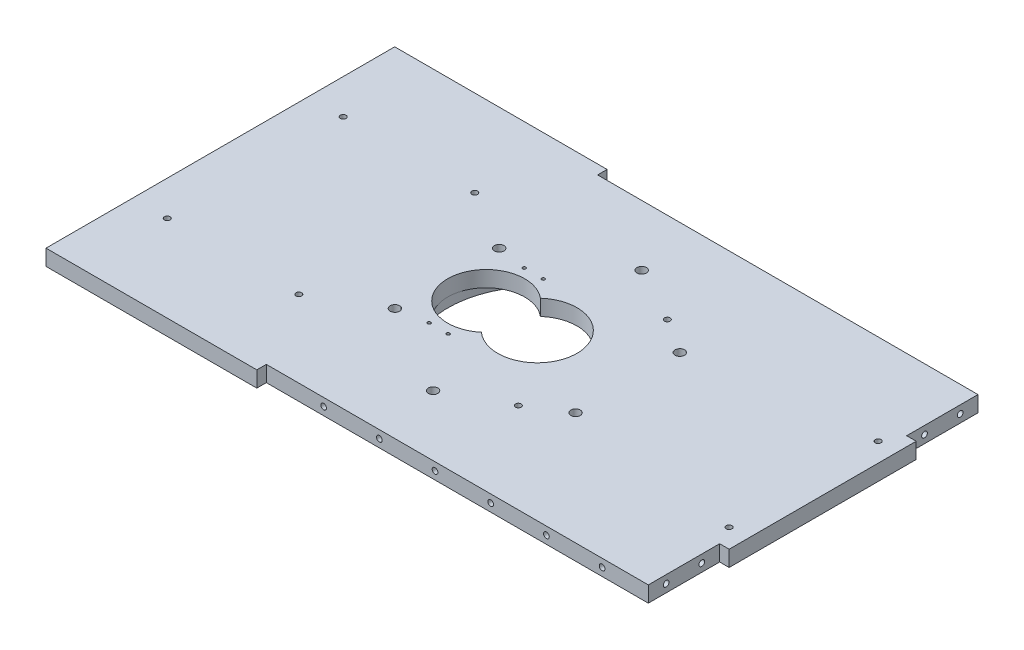
SolidWorks part; units mm, degrees
ref_plane "前视基准面" through (0, 0, 0) normal (0, 0, 1) x (1, 0, 0)
ref_plane "上视基准面" through (0, 0, 0) normal (0, 1, 0) x (1, 0, 0)
ref_plane "右视基准面" through (0, 0, 0) normal (1, 0, 0) x (0, 0, -1)
other "Configuration Table"
sketch "草图1" plane through (0, 0, 0) normal (0, 1, 0) x (1, 0, 0)
  line L0 (-100, 0) -> (90, 0)
  line L1 (-100, 55) -> (90, 55)
  line L2 (-100, 55) -> (-100, -55)
  line L3 (-100, -55) -> (90, -55)
  line L4 (90, 55) -> (90, -55)
  circle A8 centre (0, 0) radius 32.9
  circle A9 centre (0, 0) radius 34.5
  circle A10 centre (0, 0) radius 31.3
  circle A11 centre (0, 0) radius 37.5
  circle A12 centre (0, 0) radius 28.3
  circle A13 centre (-16.15, 0) radius 12.15
  circle A14 centre (0, 32.9) radius 1.5
  circle A15 centre (0, 32.9) radius 0.9
  circle A16 centre (0, 0) radius 12.5
  dimension "D3" = 110
  dimension "D4" = 90
  dimension "D1" = 65.8
  dimension "D2" = 100
  dimension "D5" = 1.6
  dimension "D6" = 1.6
  dimension "D7" = 3
  dimension "D8" = 3
  dimension "D10" = 1.8
  dimension "D11" = 3
  dimension "D12" = 25
  dimension "D9" = 16.15
extrude "凸台-拉伸1" add sketch "草图1" along normal blind 5 contours L3 L4 L1 L2
extrude "凸台-拉伸2" add sketch "草图1<10>" against normal blind 3 contours L0 A11 A9 | L0 A11 A9 | A12 L0 A10 | A12 L0 A10 region at (0, 0, -28.9999) region at (29.8, 0, 0.6999) region at (0, 0, -35.3385) region at (36, 0, 0.8385)
sketch "草图1<10>" plane through (0, 0, 0) normal (0, 1, 0) x (1, 0, 0) same geometry as "草图1"
extrude "切除-拉伸1" cut sketch "草图1<11>" against normal through all both and the other way through all contours L0 A13 | L0 A13 region at (-18.596, 0, 5.643) region at (-18.596, 0, -5.643)
sketch "草图1<11>" plane through (0, 0, 0) normal (0, 1, 0) x (1, 0, 0) same geometry as "草图1"
extrude "切除-拉伸3" cut sketch "草图1<12>" along normal through all contours A15
sketch "草图1<12>" plane through (0, 0, 0) normal (0, 1, 0) x (1, 0, 0) same geometry as "草图1"
extrude "切除-拉伸4" cut sketch "草图1<13>" against normal offset from surface (3.5 mm away) 1.5 from surface contours A14 up to face at (0, 0, 37.5) starting at face at (0, 5, -32)
sketch "草图1<13>" plane through (0, 0, 0) normal (0, 1, 0) x (1, 0, 0) same geometry as "草图1"
pattern_circular "阵列(圆周)1" count 6 over 360 about axis through (0, -3, 0) along (0, 1, 0) of "切除-拉伸3", "切除-拉伸4"
sketch "草图2" plane through (0, 5, 0) normal (0, 1, 0) x (1, 0, 0)
  line L0 (-19.15, -15) -> (-13.15, 15) construction
  line L1 (-13.15, -15) -> (-19.15, 15) construction
  circle A0 centre (-19.15, -15) radius 0.5
  circle A1 centre (-13.15, -15) radius 0.5
  circle A2 centre (-19.15, 15) radius 0.5
  circle A3 centre (-13.15, 15) radius 0.5
  circle A4 centre (-16.15, 0) radius 12.15
  circle A5 centre (-16.15, 0) radius 12.15 construction
  dimension "D1" = 1
  dimension "D2" = 15
  dimension "D3" = 3
extrude "切除-拉伸5" cut sketch "草图2" against normal blind 3 contours A0 | A1 | A2 | A3
extrude "切除-拉伸6" cut sketch "草图1<14>" against normal through all both and the other way through all contours A16
sketch "草图1<14>" plane through (0, 0, 0) normal (0, 1, 0) x (1, 0, 0) same geometry as "草图1"
sketch "草图3" plane through (0, 5, 0) normal (0, 1, 0) x (1, 0, 0)
  line L0 (90, 55) -> (90, -55) construction
  line L1 (17.5, -23.5) -> (17.5, -55) construction
  line L2 (-100, -55) -> (90, -55) construction
  line L3 (17.5, 23.5) -> (17.5, 55) construction
  line L4 (-100, 55) -> (90, 55) construction
  circle A0 centre (17.5, 23.5) radius 0.9
  circle A1 centre (17.5, -23.5) radius 0.9
  circle A2 centre (84, 23.5) radius 0.9
  circle A3 centre (84, -23.5) radius 0.9
  dimension "D1" = 1.8
  dimension "D2" = 47
  dimension "D3" = 66.5
  dimension "D4" = 6
extrude "切除-拉伸7" cut sketch "草图3" against normal blind 3
sketch "草图4" plane through (0, 5, 0) normal (0, 1, 0) x (1, 0, 0)
  circle A0 centre (-89, 27.75) radius 0.9
  circle A1 centre (-47.5, 27.75) radius 0.9
  circle A2 centre (-89, -27.75) radius 0.9
  circle A3 centre (-47.5, -27.75) radius 0.9
  dimension "D3" = 1.8
extrude "切除-拉伸8" cut sketch "草图4" against normal through all contours A2 | A3 | A1 | A0
sketch "草图5" plane through (0, 5, 0) normal (0, 1, 0) x (1, 0, 0)
  line L0 (90, 55) -> (90, -55) construction
  line L1 (90, 55) -> (-33, 55)
  line L2 (90, 55) -> (90, 52)
  line L3 (90, 52) -> (-33, 52)
  line L4 (-33, 55) -> (-33, 52)
  line L5 (-100, 55) -> (90, 55) construction
  line L6 (-100, -55) -> (90, -55) construction
  line L7 (90, -55) -> (-33.5, -55)
  line L8 (90, -55) -> (90, -52)
  line L9 (90, -52) -> (-33.5, -52)
  line L10 (-33.5, -55) -> (-33.5, -52)
  dimension "D1" = 3
  dimension "D2" = 123
extrude "切除-拉伸9" cut sketch "草图5" against normal through all
sketch "草图6" plane through (0, 0, -52) normal (0, 0, -1) x (-1, 0, 0)
  line L0 (33, 2.5) -> (15.4286, 2.5) construction
  line L1 (33, 0) -> (33, 5) construction
  line L2 (15.4286, 2.5) -> (-2.1429, 2.5) construction
  line L3 (-2.1429, 2.5) -> (-19.7143, 2.5) construction
  line L4 (-19.7143, 2.5) -> (-37.2857, 2.5) construction
  line L5 (-37.2857, 2.5) -> (-54.8571, 2.5) construction
  line L6 (-54.8571, 2.5) -> (-72.4286, 2.5) construction
  line L7 (-72.4286, 2.5) -> (-90, 2.5) construction
  line L8 (-90, 0) -> (-90, 5) construction
  circle A0 centre (15.4286, 2.5) radius 0.9
  circle A1 centre (-2.1429, 2.5) radius 0.9
  circle A2 centre (-19.7143, 2.5) radius 0.9
  circle A3 centre (-37.2857, 2.5) radius 0.9
  circle A4 centre (-54.8571, 2.5) radius 0.9
  circle A5 centre (-72.4286, 2.5) radius 0.9
  dimension "D1" = 1.8
extrude "切除-拉伸10" cut sketch "草图6" against normal blind 3
extrude "切除-拉伸11" cut sketch "草图6<2>" along normal blind 3 from surface starting at face at (28.25, 2.5, 52)
sketch "草图6<2>" plane through (0, 0, -52) normal (0, 0, -1) x (-1, 0, 0) same geometry as "草图6"
sketch "草图7" plane through (90, 0, 0) normal (1, 0, 0) x (0, 0, -1)
  line L0 (52, 5) -> (-52, 5) construction
  line L1 (52, 5) -> (29.5, 5)
  line L2 (52, 5) -> (52, 0)
  line L3 (52, 0) -> (29.5, 0)
  line L4 (29.5, 5) -> (29.5, 0)
  line L5 (52, 0) -> (-52, 0) construction
  line L6 (-52, 5) -> (-55, 5) construction
  line L7 (-52, 5) -> (-29.5, 5)
  line L8 (-52, 5) -> (-52, 0)
  line L9 (-52, 0) -> (-29.5, 0)
  line L10 (-29.5, 5) -> (-29.5, 0)
  point P15 (-54.2245, 5)
  point P17 (-49.2215, 5)
  dimension "D1" = 22.5
extrude "切除-拉伸12" cut sketch "草图7" against normal blind 3
sketch "草图8" plane through (87, 0, 0) normal (1, 0, 0) x (0, 0, -1)
  line L0 (-52, 2.5) -> (-46.375, 2.5) construction
  line L2 (-52, 5) -> (-52, 0) construction
  line L3 (-46.375, 2.5) -> (-40.75, 2.5) construction
  line L5 (-40.75, 2.5) -> (-35.125, 2.5) construction
  line L6 (-35.125, 2.5) -> (-29.5, 2.5) construction
  line L7 (-29.5, 0) -> (-29.5, 5) construction
  line L8 (29.5, 2.5) -> (35.125, 2.5) construction
  line L9 (29.5, 5) -> (29.5, 0) construction
  line L10 (35.125, 2.5) -> (40.75, 2.5) construction
  line L11 (40.75, 2.5) -> (46.375, 2.5) construction
  line L12 (46.375, 2.5) -> (52, 2.5) construction
  line L13 (52, 0) -> (52, 5) construction
  circle A0 centre (35.125, 2.5) radius 0.9
  circle A1 centre (46.375, 2.5) radius 0.9
  circle A2 centre (-46.375, 2.5) radius 0.9
  circle A3 centre (-35.125, 2.5) radius 0.9
  dimension "D1" = 1.8
extrude "切除-拉伸13" cut sketch "草图8" against normal blind 3
